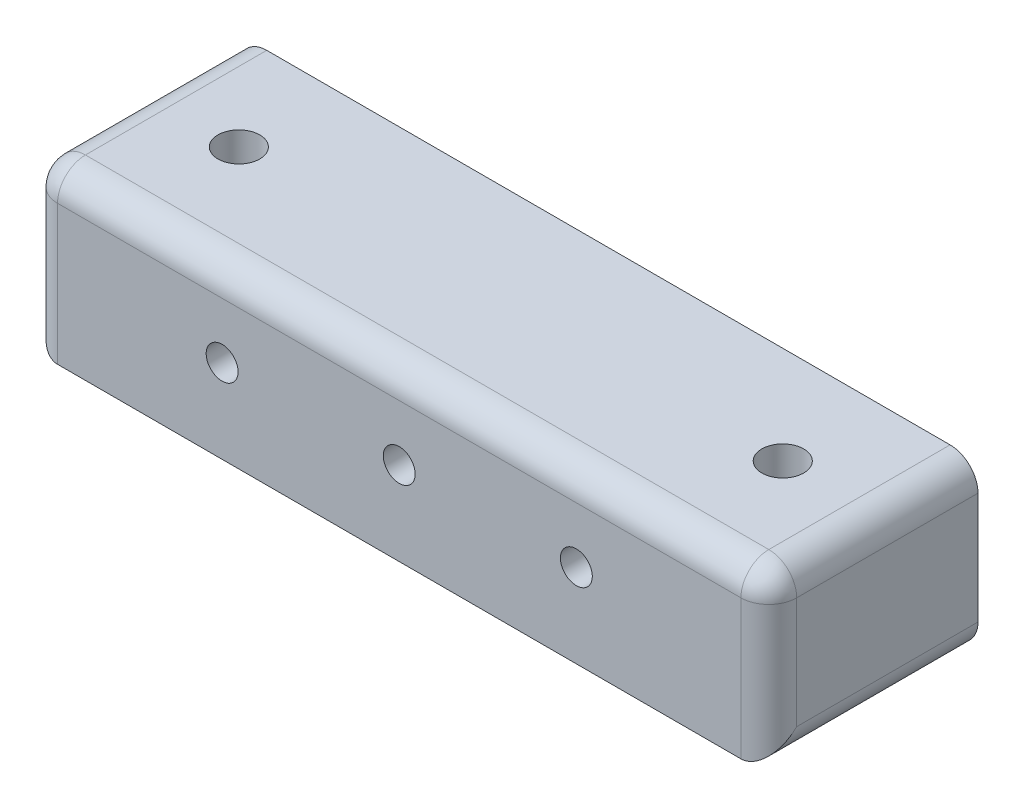
SolidWorks part; units mm, degrees
ref_plane "Front Plane" through (0, 0, 0) normal (0, 0, 1) x (1, 0, 0)
ref_plane "Top Plane" through (0, 0, 0) normal (0, 1, 0) x (1, 0, 0)
ref_plane "Right Plane" through (0, 0, 0) normal (1, 0, 0) x (0, 0, -1)
sketch "Sketch1" plane through (0, 0, 0) normal (0, 0, 1) x (1, 0, 0)
  line L1 (-26.5, 6) -> (26.5, 6)
  line L2 (-26.5, 6) -> (-26.5, -6)
  line L3 (-26.5, -6) -> (26.5, -6)
  line L4 (26.5, 6) -> (26.5, -6)
  line L5 (-26.5, 6) -> (26.5, -6) construction
  line L6 (-26.5, -6) -> (26.5, 6) construction
  point P0 (0, 0)
  dimension "D1" = 12
  dimension "D2" = 53
extrude "Boss-Extrude1" add sketch "Sketch1" along normal blind 15
sketch "Sketch2" plane through (0, -6, 0) normal (0, -1, 0) x (1, 0, 0)
  line L0 (0, 0) -> (0, 15) construction
  line L1 (-26.5, 0) -> (26.5, 0) construction
  line L2 (-26.5, 15) -> (26.5, 15) construction
  line L3 (-19.5, 7) -> (19.5, 7) construction
  circle A0 centre (-19.5, 7) radius 1.5
  circle A1 centre (19.5, 7) radius 1.5
  point P8 (0, 7)
  dimension "D1" = 3
  dimension "D2" = 39
  dimension "D3" = 8
extrude "Cut-Extrude1" cut sketch "Sketch2" against normal up to next
fillet "Fillet1" radius 2 7 edges at (26.5, 0, 15) (0, 6, 15) (-26.5, 0, 15) (-26.5, 6, 7.5) (26.5, 6, 7.5) (26.5, -6, 7.5) (-26.5, -6, 7.5)
sketch "Sketch3" plane through (0, 0, 0) normal (0, 0, -1) x (-1, 0, 0)
  line L0 (0, 6) -> (0, -6) construction
  line L1 (-24.5, 6) -> (24.5, 6) construction
  line L2 (24.5, -6) -> (-24.5, -6) construction
  line L3 (-26.5, 0) -> (26.5, 0) construction
  line L4 (26.5, 4) -> (26.5, -4) construction
  circle A0 centre (-12.7, 0) radius 1.143
  circle A1 centre (12.7, 0) radius 1.143
  circle A2 centre (0, 0) radius 1.143
  point P12 (0, 0)
  dimension "D1" = 2.286
  dimension "D2" = 25.4
  dimension "D3" = 12.7
extrude "Cut-Extrude2" cut sketch "Sketch3" against normal through all
